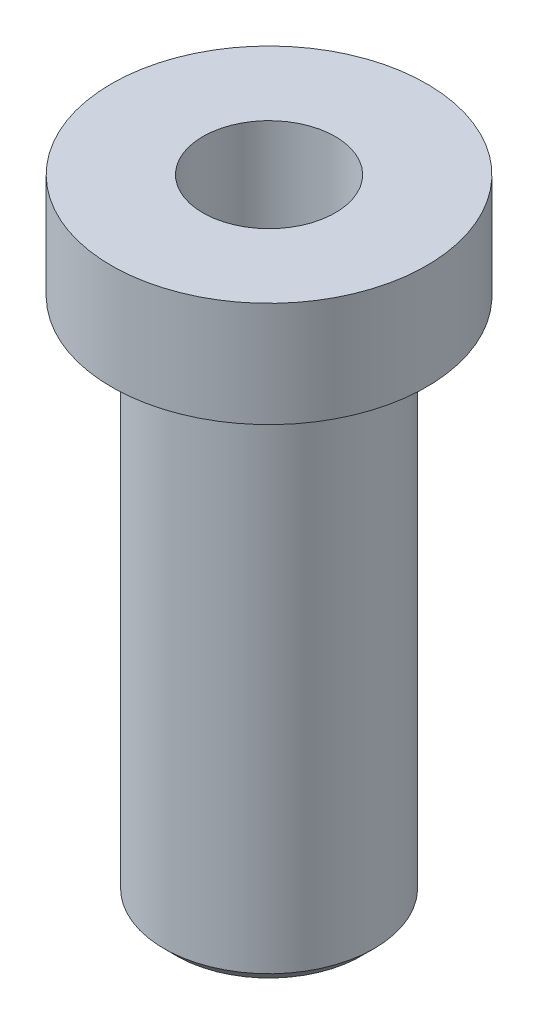
SolidWorks part; units mm, degrees
ref_plane "Front Plane" through (0, 0, 0) normal (0, 0, 1) x (1, 0, 0)
ref_plane "Top Plane" through (0, 0, 0) normal (0, 1, 0) x (1, 0, 0)
ref_plane "Right Plane" through (0, 0, 0) normal (1, 0, 0) x (0, 0, -1)
sketch "Sketch1" plane through (0, 0, 0) normal (0, 0, 1) x (1, 0, 0)
  line L0 (0, 38.1) -> (0, -38.1) construction
  line L1 (-27.3369, 0) -> (14.165, 0) construction
  line L2 (12.7, -38.1) -> (12.7, 25.4)
  line L3 (12.7, 25.4) -> (19.05, 25.4)
  line L4 (19.05, 25.4) -> (19.05, 38.1)
  line L5 (19.05, 38.1) -> (8.001, 38.1)
  line L6 (8.001, 38.1) -> (8.001, -38.1)
  line L7 (8.001, -38.1) -> (12.7, -38.1)
  point P10 (0, 0)
  point P12 (14.165, 0)
  point P13 (2.3885, 39.5104)
  point P14 (19.05, 31.75)
  dimension "D1" = 76.2
  dimension "D2" = 63.5
  dimension "D3" = 12.7
  dimension "D4" = 38.1
  dimension "D5" = 16.002
  dimension "D6" = 25.4
  dimension "D7" = 38.1
revolve "Revolve2" add sketch "Sketch1" angle 360 about L0
chamfer "Chamfer1" distance 1.524 angle 45 1 edges at (-12.7, -38.1, 0)
